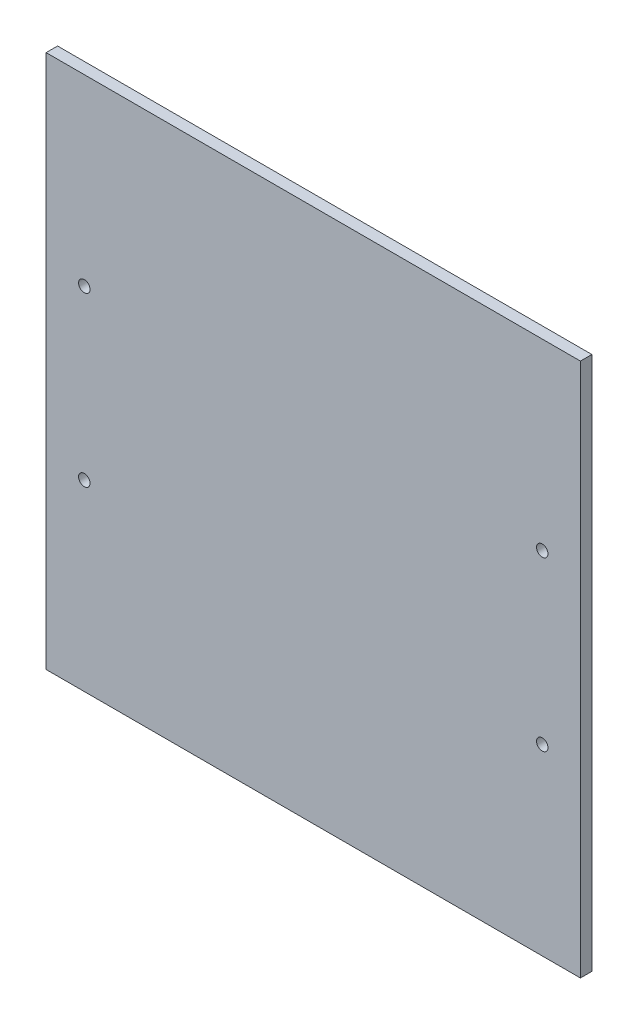
SolidWorks part; units mm, degrees
material "Ceramic Porcelain"
ref_plane "Front Plane" through (0, 0, 0) normal (0, 0, 1) x (1, 0, 0)
ref_plane "Top Plane" through (0, 0, 0) normal (0, 1, 0) x (1, 0, 0)
ref_plane "Right Plane" through (0, 0, 0) normal (1, 0, 0) x (0, 0, -1)
sketch "Sketch1" plane through (0, 0, 0) normal (0, 0, 1) x (1, 0, 0)
  line L0 (140, 70) -> (0, 70) construction
  line L1 (0, 0) -> (140, 0)
  line L2 (0, 0) -> (0, 140)
  line L3 (0, 140) -> (140, 140)
  line L4 (140, 0) -> (140, 140)
  dimension "D1" = 140
  dimension "D5" = 140
extrude "Boss-Extrude1" add sketch "Sketch1" along normal blind 3
hole_wizard "M3x0.5 Tapped Hole1" positions "Sketch6" profile "Sketch5" tap size "M3x0.5" standard "Ansi Metric" end condition through all
sketch "Sketch6" plane through (0, 0, 0) normal (0, 0, -1) x (-1, 0, 0)
  line L0 (6.0733, 70) -> (-132.5, 70) construction
  line L5 (-130, 92) -> (-130, 48) construction
  line L9 (-70, 140) -> (-70, 0) construction
  line L10 (-140, 140) -> (0, 140) construction
  line L11 (0, 0) -> (-140, 0) construction
  line L13 (-10, 92) -> (-10, 48) construction
  line L14 (-146.0733, 70) -> (-7.5, 70) construction
  point P20 (-130, 92)
  point P22 (-130, 48)
  point P48 (-10, 92)
  point P50 (-10, 48)
  dimension "D1" = 60
  dimension "D3" = 22
  dimension "D4" = 44
sketch "Sketch5" plane through (130, 92, 0) normal (1, 0, 0) x (0, 1, 0)
  line L0 (0, 0) -> (0, 3)
  line L1 (0, 3) -> (1.5, 3)
  line L2 (1.5, 3) -> (1.5, 0)
  line L5 (1.5, 0) -> (0, 0)
  line L11 (0, -6.35) -> (0, 107.95) construction
  dimension "Thread Major Dia." = 3
  dimension "Thru Tap Drill Depth" = 3
sketch "Sketch7" plane through (0, 0, 0) normal (0, 0, -1) x (-1, 0, 0)
  line L0 (-70, 140) -> (-70, 0) construction
  line L1 (-140, 140) -> (0, 140) construction
  line L2 (0, 0) -> (-140, 0) construction
  line L3 (-61.8, 132) -> (-78.2, 132) construction
  circle A0 centre (-78.2, 132) radius 1.5
  circle A1 centre (-61.8, 132) radius 1.5
  dimension "D2" = 3
  dimension "D3" = 8.2
  dimension "D1" = 8.2
  dimension "D4" = 8
extrude "Cut-Extrude1" [suppressed] cut sketch "Sketch7" against normal through all
sketch "Sketch8" plane through (0, 0, 0) normal (0, 0, -1) x (-1, 0, 0)
  line L0 (-140, 70) -> (0, 70) construction
  line L1 (-140, 0) -> (-140, 140) construction
  line L2 (0, 140) -> (0, 0) construction
  circle A0 centre (-70, 70) radius 3
  dimension "D1" = 6
extrude "Cut-Extrude2" cut sketch "Sketch8" against normal blind 2
